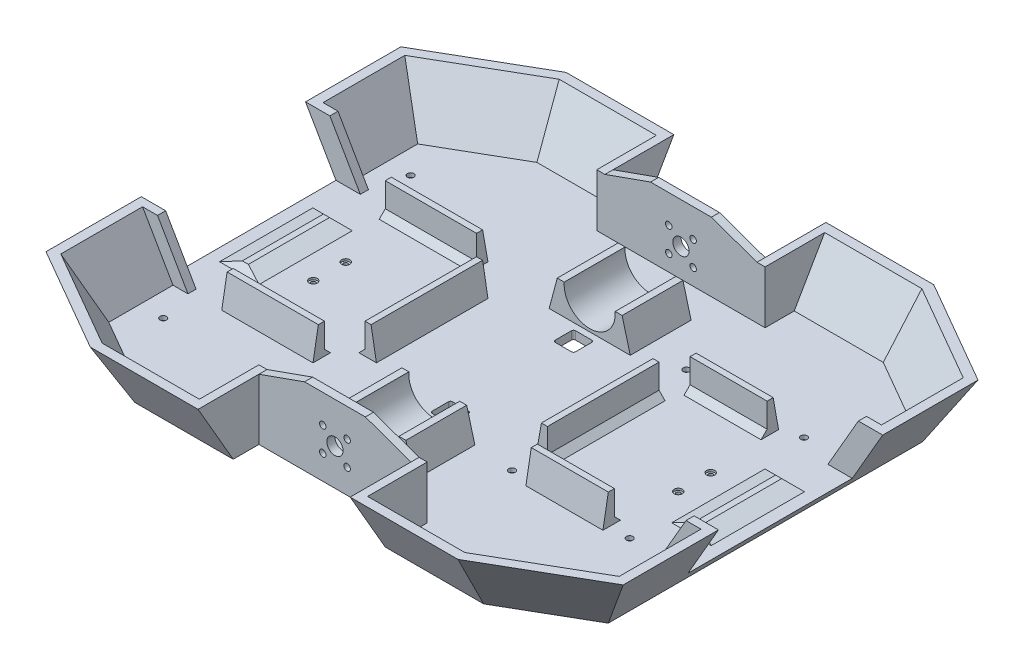
SolidWorks part; units mm, degrees
ref_plane "Front Plane" through (0, 0, 0) normal (0, 0, 1) x (1, 0, 0)
ref_plane "Top Plane" through (0, 0, 0) normal (0, 1, 0) x (1, 0, 0)
ref_plane "Right Plane" through (0, 0, 0) normal (1, 0, 0) x (0, 0, -1)
sketch "Sketch1" plane through (0, 0, 0) normal (0, 1, 0) x (1, 0, 0)
  line L0 (-125, 77.5) -> (-86.0289, 100)
  line L1 (-125, 100) -> (125, 100) construction
  line L2 (-125, 100) -> (-125, -100) construction
  line L3 (-125, -100) -> (125, -100) construction
  line L4 (125, 100) -> (125, -100) construction
  line L5 (-86.0289, 100) -> (86.0289, 100)
  line L6 (-125, 77.5) -> (-125, -77.5)
  line L7 (0, 100) -> (0, -100) construction
  line L8 (-125, 0) -> (125, 0) construction
  line L9 (125, 77.5) -> (125, -77.5)
  line L10 (125, 77.5) -> (86.0289, 100)
  line L11 (125, -77.5) -> (86.0289, -100)
  line L12 (-86.0289, -100) -> (86.0289, -100)
  line L13 (-125, -77.5) -> (-86.0289, -100)
  point P4 (0, 100)
  point P6 (-125, 0)
  dimension "D1" = 200
  dimension "D2" = 250
  dimension "D3" = 30
  dimension "D4" = 45
extrude "Boss-Extrude1" add sketch "Sketch1" along normal blind 30
draft "Draft1" type of draft neutral plane draft angle 30 faces to draft 8 face at (-105.5144, 15, 88.75) face at (0, 15, 100) face at (105.5144, 15, 88.75) face at (125, 15, 0) face at (105.5144, 15, -88.75) face at (0, 15, -100) face at (-105.5144, 15, -88.75) face at (-125, 15, 0) neutral plane through (0, 0, 0) neutral plane normal (0, -1, 0) parameters "D1"=30
shell "Shell1" thickness 4 removed face at (0, 30, 0)
sketch "Sketch2" plane through (0, 30, 0) normal (0, 1, 0) x (1, 0, 0)
  line L0 (142.3205, 0) -> (-142.3205, 0) construction
  line L1 (142.3205, -87.5) -> (142.3205, 87.5) construction
  line L2 (-142.3205, 87.5) -> (-142.3205, -87.5) construction
  line L3 (-90.6699, -117.3205) -> (90.6699, -117.3205) construction
  line L4 (-37.5, -117.3205) -> (37.5, -117.3205)
  line L5 (-37.5, -117.3205) -> (-37.5, -87.3205)
  line L6 (-37.5, -87.3205) -> (37.5, -87.3205)
  line L7 (37.5, -117.3205) -> (37.5, -87.3205)
  point P12 (0, -87.3205)
  dimension "D1" = 30
  dimension "D2" = 75
extrude "Cut-Extrude1" cut sketch "Sketch2" against normal through all
sketch "Sketch3" plane through (0, 0, 87.3205) normal (0, 0, 1) x (1, 0, 0)
  line L0 (37.5, 4) -> (-37.5, 4) construction
  line L1 (-15, 4) -> (15, 4) construction
  line L2 (-15, 4) -> (-15, 38) construction
  line L3 (-15, 38) -> (15, 38) construction
  line L4 (15, 4) -> (15, 38) construction
  line L5 (-37.5, 4) -> (-37.5, 30)
  line L6 (-37.5, 30) -> (-15, 38)
  line L7 (-15, 38) -> (15, 38)
  line L8 (15, 38) -> (37.5, 30)
  line L9 (37.5, 30) -> (37.5, 4)
  line L10 (37.5, 4) -> (-37.5, 4)
  point P6 (0, 4)
  point P7 (0, 4)
  dimension "D1" = 30
  dimension "D2" = 34
extrude "Boss-Extrude2" add sketch "Sketch3" against normal blind 4
sketch "Sketch4" plane through (37.5, 0, 0) normal (1, 0, 0) x (0, 0, -1)
  line L4 (-83.3205, 30) -> (-117.3205, 30)
  line L5 (-117.3205, 30) -> (-100, 0)
  line L6 (-100, 0) -> (-83.3205, 0)
  line L7 (-83.3205, 0) -> (-83.3205, 30)
extrude "Boss-Extrude4" add sketch "Sketch4" along normal blind 4
mirror "Mirror1" about plane through (0, 0, 0) normal (1, 0, 0) of "Boss-Extrude4"
sketch "Sketch5" plane through (0, 0, 87.3205) normal (0, 0, 1) x (1, 0, 0)
  line L1 (37.5, 0) -> (-37.5, 0) construction
  point P4 (0, 0)
  line B0 (-6.0104, 11.9896) -> (6.0104, 24.0104) construction
  circle B1 centre (0, 18) radius 4
  circle B2 centre (-6.0104, 11.9896) radius 1.6
  circle B3 centre (6.0104, 24.0104) radius 1.6
  circle B4 centre (0, 18) radius 12.5 construction
  line B5 (6.0104, 11.9896) -> (-6.0104, 24.0104) construction
  circle B6 centre (0, 18) radius 4
  circle B7 centre (6.0104, 11.9896) radius 1.6
  circle B8 centre (-6.0104, 24.0104) radius 1.6
  circle B9 centre (0, 18) radius 12.5 construction
  dimension "D1" = 18
sketch_block_instance "Block-JGA25-371-4"
sketch_block "Block-JGA25-371" parameters "D1"=8, "D3"=3.2, "D4"=25, "D2"=17
sketch_block_instance "Block-JGA25-371-5"
extrude "Cut-Extrude2" cut sketch "Sketch5" against normal blind 5 contours B8 | B3 | B7 | B2 | B1 | B6 region at (0, 18, 87.3205) region at (-6.0104, 11.9896, 87.3205) region at (6.0104, 24.0104, 87.3205) region at (6.0104, 11.9896, 87.3205) region at (-6.0104, 24.0104, 87.3205)
sketch "Sketch9" plane through (0, 4, 0) normal (0, 1, 0) x (1, 0, 0)
  line L1 (-15, -38.3205) -> (15, -38.3205)
  line L2 (-15, -38.3205) -> (-15, -68.3205)
  line L3 (-15, -68.3205) -> (15, -68.3205)
  line L4 (15, -38.3205) -> (15, -68.3205)
  line L6 (-41.5, -83.3205) -> (41.5, -83.3205) construction
  point P4 (0, -38.3205)
  dimension "D1" = 30
  dimension "D2" = 30
  dimension "D3" = 15
extrude "Boss-Extrude5" add sketch "Sketch9" along normal blind 15
sketch "Sketch10" plane through (0, 0, 68.3205) normal (0, 0, 1) x (1, 0, 0)
  circle A0 centre (0, 18) radius 12.6
  point P2 (0, 18)
  dimension "D1" = 25.2
extrude "Cut-Extrude5" cut sketch "Sketch10" against normal up to next
chamfer "Chamfer4" distance 5 angle 75 2 edges at (-15, 4, 53.3205) (15, 4, 53.3205) first distance on face at (0, 4, 30.1685)
sketch "Sketch15" plane through (0, 4, 0) normal (0, 1, 0) x (1, 0, 0)
  line L0 (-41.5, -83.3205) -> (41.5, -83.3205) construction
  line L1 (-5, -25.3205) -> (5, -25.3205)
  line L2 (-5, -25.3205) -> (-5, -35.3205)
  line L3 (-5, -35.3205) -> (5, -35.3205)
  line L4 (5, -25.3205) -> (5, -35.3205)
  point P4 (0, -25.3205)
  dimension "D1" = 10
  dimension "D2" = 48
extrude "Cut-Extrude8" cut sketch "Sketch15" against normal through all
fillet "Fillet1" radius 1 4 edges at (5, 2, 25.3205) (5, 2, 35.3205) (-5, 2, 25.3205) (-5, 2, 35.3205)
mirror "Mirror4" about plane through (0, 0, 0) normal (0, 0, 1) of "Mirror1", "Cut-Extrude1", "Cut-Extrude2", "Boss-Extrude2", "Boss-Extrude4", "Boss-Extrude5", "Chamfer4", "Cut-Extrude5", "Cut-Extrude8", "Fillet1"
ref_plane "Plane3" through (0, -15, 0) normal (0, -1, 0) x (-1, 0, 0)
sketch "Sketch16" plane through (0, 0, 0) normal (0, -1, 0) x (1, 0, 0)
  line L0 (-90, 0) -> (90, 0) construction
  point P5 (0, 0)
  circle B0 centre (-90, -8) radius 1.1
  circle B1 centre (-90, 8) radius 1.1
  circle B2 centre (90, -8) radius 1.1
  circle B3 centre (90, 8) radius 1.1
  dimension "D1" = 180
sketch_block_instance "Ball-Caster-1"
sketch_block "Ball-Caster" parameters "D1"=16, "D2"=2.2, "D3"=16
sketch_block_instance "Ball-Caster-2"
extrude "Cut-Extrude9" cut sketch "Sketch16" against normal up to next
sketch "Sketch17" plane through (0, 4, 0) normal (0, 1, 0) x (1, 0, 0)
  circle A0 centre (-90, 8) radius 2
  circle A1 centre (-90, -8) radius 2
  circle A2 centre (90, 8) radius 2
  circle A3 centre (90, -8) radius 2
  dimension "D1" = 4
extrude "Cut-Extrude10" cut sketch "Sketch17" against normal blind 1
sketch "Sketch6" plane through (0, 4, 0) normal (0, 1, 0) x (1, 0, 0)
  line L0 (-111, 61) -> (-24, 61) construction
  line L1 (-24, 61) -> (-24, -61) construction
  line L2 (-24, -61) -> (-111, -61) construction
  line L3 (-111, -61) -> (-111, 61) construction
  line L4 (-115, 65) -> (-20, 65) construction
  line L5 (-20, 65) -> (-20, -65) construction
  line L6 (-20, -65) -> (-115, -65) construction
  line L7 (-115, -65) -> (-115, 65) construction
  circle A0 centre (-111, 61) radius 1.6
  circle A1 centre (-24, 61) radius 1.6
  circle A2 centre (-111, -61) radius 1.6
  circle A3 centre (-24, -61) radius 1.6
  point P12 (-20, 0)
  dimension "D1" = 3.2
  dimension "D2" = 87
  dimension "D3" = 122
  dimension "D5" = 20
  dimension "D4" = 4
extrude "Cut-Extrude3" cut sketch "Sketch6" against normal blind 5
sketch "Sketch7" plane through (0, 0, 0) normal (0, -1, 0) x (1, 0, 0)
  circle A0 centre (-111, 61) radius 3.5
  circle A1 centre (-24, 61) radius 3.5
  circle A2 centre (-24, -61) radius 3.5
  circle A3 centre (-111, -61) radius 3.5
  dimension "D1" = 7
extrude "Cut-Extrude4" cut sketch "Sketch7" against normal blind 2 contours A0 | A1 | A2 | A3
sketch "Sketch19" plane through (0, 4, 0) normal (0, 1, 0) x (1, 0, 0)
  line B0 (23, -50) -> (23, 50) construction
  line B1 (102, -50) -> (102, 50) construction
  line B2 (40, -40) -> (40, 46) construction
  circle B3 centre (40, -40) radius 1.6
  circle B4 centre (98, -40) radius 1.6
  circle B5 centre (40, 46) radius 1.6
  circle B6 centre (98, 46) radius 1.6
  dimension "D1" = 23
sketch_block_instance "Block-Jetson-Nano-1"
sketch_block "Block-Jetson-Nano" parameters "D3"=3.2, "D1"=100, "D2"=79, "D4"=4, "D5"=10, "D6"=17, "D7"=4
extrude "Cut-Extrude11" cut sketch "Sketch19" against normal through all
sketch "Sketch20" plane through (0, 0, 0) normal (0, -1, 0) x (1, 0, 0)
  circle A0 centre (98, 40) radius 3.5
  circle A1 centre (40, 40) radius 3.5
  circle A2 centre (98, -46) radius 3.5
  circle A3 centre (40, -46) radius 3.5
  dimension "D1" = 7
extrude "Cut-Extrude12" cut sketch "Sketch20" against normal blind 2
sketch "Sketch18" plane through (0, 4, 0) normal (0, 1, 0) x (1, 0, 0)
  line L0 (-113, 40.5) -> (-42, 40.5) construction
  line L1 (-110, 37.5) -> (-45, 37.5) construction
  line L2 (-110, 37.5) -> (-110, -37.5) construction
  line L3 (-110, -37.5) -> (-45, -37.5) construction
  line L4 (-45, 37.5) -> (-45, -37.5) construction
  line L5 (45, 37.5) -> (110, 37.5) construction
  line L6 (45, 37.5) -> (45, -37.5) construction
  line L7 (45, -37.5) -> (110, -37.5) construction
  line L8 (110, 37.5) -> (110, -37.5) construction
  line L9 (-42, 40.5) -> (-42, -40.5) construction
  line L10 (-113, -40.5) -> (-42, -40.5) construction
  line L11 (-113, 40.5) -> (-113, -40.5) construction
  line L12 (42, 40.5) -> (113, 40.5) construction
  line L13 (-100, 40.5) -> (-55, 40.5)
  line L14 (-100, 40.5) -> (-100, 37.5)
  line L15 (-100, 37.5) -> (-55, 37.5)
  line L16 (-55, 40.5) -> (-55, 37.5)
  line L17 (-100, -37.5) -> (-55, -37.5)
  line L18 (-100, -37.5) -> (-100, -40.5)
  line L19 (-100, -40.5) -> (-55, -40.5)
  line L20 (-55, -37.5) -> (-55, -40.5)
  line L21 (-110, 27.5) -> (-113, 27.5) construction
  line L22 (-110, 27.5) -> (-110, -27.5) construction
  line L23 (-110, -27.5) -> (-113, -27.5) construction
  line L24 (-113, 27.5) -> (-113, -27.5) construction
  line L25 (-45, 27.5) -> (-42, 27.5)
  line L26 (-45, 27.5) -> (-45, -27.5)
  line L27 (-45, -27.5) -> (-42, -27.5)
  line L28 (-42, 27.5) -> (-42, -27.5)
  line L29 (113, 40.5) -> (113, -40.5) construction
  line L30 (42, -40.5) -> (113, -40.5) construction
  line L31 (42, 40.5) -> (42, -40.5) construction
  line L33 (88, -37.5) -> (50, -37.5)
  line L34 (88, -37.5) -> (88, -40.5)
  line L35 (88, -40.5) -> (50, -40.5)
  line L36 (50, -37.5) -> (50, -40.5)
  line L37 (45, -27.5) -> (42, -27.5)
  line L38 (45, -27.5) -> (45, 27.5)
  line L39 (45, 27.5) -> (42, 27.5)
  line L40 (42, -27.5) -> (42, 27.5)
  line L41 (113, 27.5) -> (110, 27.5) construction
  line L42 (113, 27.5) -> (113, -27.5) construction
  line L43 (113, -27.5) -> (110, -27.5) construction
  line L44 (110, 27.5) -> (110, -27.5) construction
  line L49 (50.3205, 40.5) -> (88.3205, 40.5)
  line L50 (50.3205, 40.5) -> (50.3205, 37.5)
  line L51 (50.3205, 37.5) -> (88.3205, 37.5)
  line L52 (88.3205, 40.5) -> (88.3205, 37.5)
  point P4 (-45, 0)
  point P10 (45, 0)
  point P31 (-110, 0)
  point P32 (-45, 0)
  point P33 (-77.5, -37.5)
  point P34 (-77.5, 37.5)
  point P35 (-77.5, 37.5)
  point P44 (98, -40)
  point P45 (40, -40)
  point P62 (113, 0)
  point P63 (45, 0)
  dimension "D1" = 65
  dimension "D2" = 75
  dimension "D3" = 45
  dimension "D4" = 45
  dimension "D6" = 45
  dimension "D7" = 55
  dimension "D9" = 10
  dimension "D10" = 10
  dimension "D11" = 55
  dimension "D5" = 3
  dimension "D8" = 3
extrude "Boss-Extrude8" add sketch "Sketch18" along normal blind 15
chamfer "Chamfer9" distance 15 angle 10 6 edges at (42, 4, 0) (69, 4, 40.5) (-77.5, 4, -40.5) (-77.5, 4, 40.5) (-42, 4, 0) (69.3205, 4, -40.5) first distance on face at (42, 11.5, 0) first distance on face at (69, 11.5, 40.5) first distance on face at (-77.5, 11.5, -40.5) first distance on face at (-77.5, 11.5, 40.5) first distance on face at (-42, 11.5, 0) first distance on face at (69.3205, 11.5, -40.5)
chamfer "Chamfer13" distance 3 angle 45 6 edges at (45, 4, 0) (69, 4, 37.5) (-77.5, 4, 37.5) (-45, 4, 0) (-77.5, 4, -37.5) (69.3205, 4, -37.5)
sketch "Sketch21" plane through (0, 4, 0) normal (0, 1, 0) x (1, 0, 0)
  line L0 (-100, 37.5) -> (-55, 37.5) construction
  line L1 (-45, 37.5) -> (-110, 37.5) construction
  line L2 (-45, 37.5) -> (-45, -37.5) construction
  line L3 (-45, -37.5) -> (-110, -37.5) construction
  line L4 (-110, 37.5) -> (-110, -37.5) construction
  line L5 (-55, -37.5) -> (-100, -37.5) construction
  line L6 (-45, 27.5) -> (-45, -27.5) construction
  line L7 (45, -27.5) -> (45, 27.5) construction
  line L8 (45, 37.5) -> (110, 37.5) construction
  line L9 (45, 37.5) -> (45, -37.5) construction
  line L10 (45, -37.5) -> (110, -37.5) construction
  line L11 (110, 37.5) -> (110, -37.5) construction
  line L13 (88, -37.5) -> (50, -37.5) construction
  line L14 (50.3205, 37.5) -> (88.3205, 37.5) construction
  line L15 (-110, 20) -> (-113, 20)
  line L16 (-110, 20) -> (-110, -20)
  line L17 (-110, -20) -> (-113, -20)
  line L18 (-113, 20) -> (-113, -20)
  line L19 (110, 20) -> (113, 20)
  line L20 (110, 20) -> (110, -20)
  line L21 (110, -20) -> (113, -20)
  line L22 (113, 20) -> (113, -20)
  point P24 (-110, 0)
  point P25 (-110, 0)
  point P30 (113, 0)
  point P31 (110, 0)
  dimension "D1" = 65
  dimension "D2" = 65
  dimension "D3" = 3
  dimension "D4" = 40
extrude "Boss-Extrude9" add sketch "Sketch21" along normal blind 3
chamfer "Chamfer10" distance 3 angle 70 4 edges at (113, 4, 0) (110, 4, 0) (-110, 4, 0) (-113, 4, 0) first distance on face at (113, 5.5, 0) first distance on face at (110, 5.5, 0) first distance on face at (-110, 5.5, 0) first distance on face at (-113, 5.5, 0)
chamfer "Chamfer11" distance 3 angle 45 4 edges at (111.5, 4, -20) (-111.5, 4, 20) (-111.5, 4, -20) (111.5, 4, 20)
ref_plane "Plane4" through (-142.3205, 0, 0) normal (-1, 0, 0) x (0, 0, 1)
sketch "Sketch22" plane through (-142.3205, 0, 0) normal (-1, 0, 0) x (0, 0, 1)
  line L0 (-87.5, 30) -> (87.5, 30) construction
  line L1 (-40.5, 30) -> (40.5, 30)
  line L2 (-40.5, 30) -> (-40.5, 4)
  line L3 (-40.5, 4) -> (40.5, 4)
  line L4 (40.5, 30) -> (40.5, 4)
  point P6 (0, 4)
  dimension "D1" = 81
  dimension "D2" = 26
extrude "Cut-Extrude13" cut sketch "Sketch22" against normal up to vertex (19.6299 mm away) up to point (-122.6906, 4, -76.1667)
mirror "Mirror5" about plane through (0, 0, 0) normal (1, 0, 0) of "Cut-Extrude13"
sketch "Sketch23" plane through (0, 0, 40.5) normal (0, 0, -1) x (-1, 0, 0)
  line L0 (-142.3205, 30) -> (-127.3094, 4)
  line L1 (-127.3094, 4) -> (-115.3094, 4)
  line L2 (-115.3094, 4) -> (-130.3205, 30)
  line L3 (-130.3205, 30) -> (-142.3205, 30)
  dimension "D1" = 12
extrude "Boss-Extrude10" add sketch "Sketch23" against normal blind 4
mirror "Mirror6" about plane through (0, 0, 0) normal (0, 0, 1) of "Boss-Extrude10" second plane through (0, 0, 0) second plane normal (1, 0, 0)
